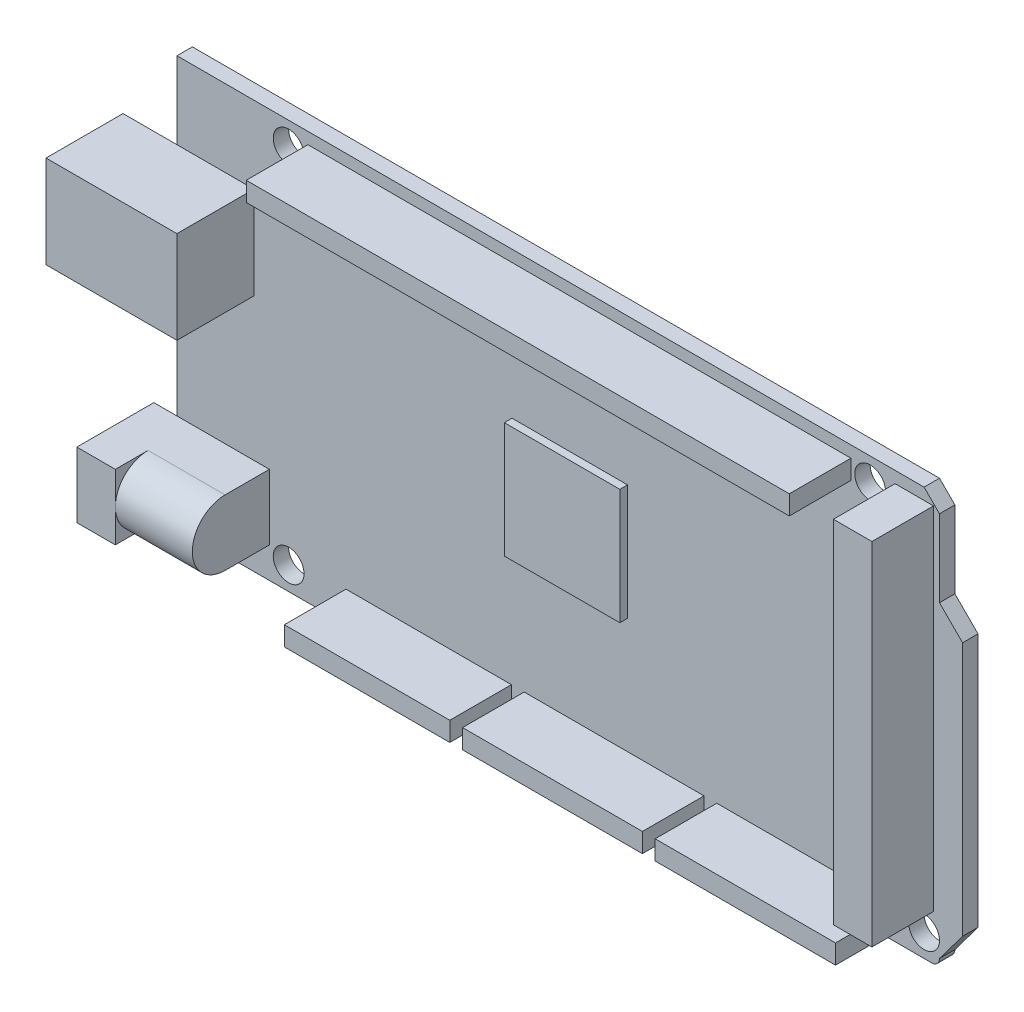
SolidWorks part; units mm, degrees
ref_plane "前视基准面" through (0, 0, 0) normal (0, 0, 1) x (1, 0, 0)
ref_plane "上视基准面" through (0, 0, 0) normal (0, 1, 0) x (1, 0, 0)
ref_plane "右视基准面" through (0, 0, 0) normal (1, 0, 0) x (0, 0, -1)
sketch "草图2" plane through (0, 0, 0) normal (0, 0, 1) x (1, 0, 0)
  line L1 (-51, 26.5) -> (51, 26.5)
  line L2 (-51, 26.5) -> (-51, -26.5)
  line L3 (-51, -26.5) -> (51, -26.5)
  line L4 (51, 26.5) -> (51, -26.5)
  line L5 (-51, 26.5) -> (51, -26.5) construction
  line L6 (-51, -26.5) -> (51, 26.5) construction
  point P0 (0, 0)
  dimension "D1" = 102
  dimension "D2" = 53
extrude "凸台-拉伸1" add sketch "草图2" along normal blind 2
sketch "草图3" plane through (0, 0, 2) normal (0, 0, 1) x (1, 0, 0)
  line L0 (51, 11.5) -> (48, 14.5)
  line L2 (48, 14.5) -> (48, 24.5)
  line L3 (51, -26.5) -> (51, 26.5) construction
  line L5 (51, -21.5) -> (48, -25.5)
  line L6 (48, -25.5) -> (48, -26.5)
  line L7 (-51, -26.5) -> (51, -26.5) construction
  line L8 (48, 24.5) -> (46, 26.5)
  line L9 (51, 26.5) -> (-51, 26.5) construction
  line L10 (48, -26.5) -> (51, -26.5)
  line L11 (51, -26.5) -> (51, -21.5)
  line L12 (46, 26.5) -> (51, 26.5)
  line L13 (51, 26.5) -> (51, 11.5)
  dimension "D1" = 15
  dimension "D2" = 3
  dimension "D3" = 135
  dimension "D4" = 2
  dimension "D5" = 3
  dimension "D6" = 3
  dimension "D7" = 5
  dimension "D8" = 1
extrude "切除-拉伸1" cut sketch "草图3" against normal blind 2
sketch "草图4" plane through (0, 0, 2) normal (0, 0, 1) x (1, 0, 0)
  line L0 (-51, -26.5) -> (48, -26.5) construction
  line L1 (51, -21.5) -> (51, 11.5) construction
  circle A0 centre (46, -23.5) radius 2
  dimension "D2" = 4
  dimension "D1" = 3
  dimension "D3" = 5
extrude "切除-拉伸2" cut sketch "草图4" against normal blind 2
fillet "圆角1" radius 1 1 edges at (48, -26.5, 1)
sketch "草图5" plane through (0, 0, 2) normal (0, 0, 1) x (1, 0, 0)
  line L0 (48, 24.5) -> (48, 14.5) construction
  line L1 (46, 26.5) -> (-51, 26.5) construction
  line L2 (-51, 26.5) -> (-51, -26.5) construction
  line L3 (-51, 0) -> (-23.0859, 0) construction
  circle A0 centre (39, 23.5) radius 2
  circle A1 centre (-36.5, 23.5) radius 2
  circle A2 centre (-36.5, -23.5) radius 2
  dimension "D1" = 4
  dimension "D6" = 4
  dimension "D2" = 9
  dimension "D3" = 3
  dimension "D4" = 3
  dimension "D5" = 14.5
extrude "切除-拉伸3" cut sketch "草图5" against normal blind 2
sketch "草图6" plane through (0, 0, 2) normal (0, 0, 1) x (1, 0, 0)
  line L0 (46, 26.5) -> (-51, 26.5) construction
  line L1 (-58, 16.5) -> (-41, 16.5)
  line L2 (-58, 16.5) -> (-58, 4.5)
  line L3 (-58, 4.5) -> (-41, 4.5)
  line L4 (-41, 16.5) -> (-41, 4.5)
  line L5 (-51, 26.5) -> (-51, -26.5) construction
  dimension "D1" = 12
  dimension "D2" = 10
  dimension "D3" = 10
  dimension "D4" = 17
extrude "凸台-拉伸2" add sketch "草图6" along normal blind 10
sketch "草图7" plane through (0, 0, 2) normal (0, 0, 1) x (1, 0, 0)
  line L0 (46, 26.5) -> (-51, 26.5) construction
  line L1 (-34, 25) -> (36.5, 25)
  line L2 (-34, 25) -> (-34, 22.5)
  line L3 (-34, 22.5) -> (36.5, 22.5)
  line L4 (36.5, 25) -> (36.5, 22.5)
  line L5 (-51, -26.5) -> (47, -26.5) construction
  line L6 (42.2266, 25) -> (47.2266, 25)
  line L7 (42.2266, 25) -> (42.2266, -20.5979)
  line L8 (42.2266, -20.5979) -> (47.2266, -20.5979)
  line L9 (47.2266, 25) -> (47.2266, -20.5979)
  line L10 (-29.0529, -22.5) -> (42.5, -22.5)
  line L11 (-29.0529, -22.5) -> (-29.0529, -25)
  line L12 (-29.0529, -25) -> (42.5, -25)
  line L13 (42.5, -22.5) -> (42.5, -25)
  circle A0 centre (39, 23.5) radius 2 construction
  circle A1 centre (-36.5, 23.5) radius 2 construction
  circle A2 centre (46, -23.5) radius 2 construction
  dimension "D8" = 3.5
  dimension "D1" = 2.5
  dimension "D2" = 1.5
  dimension "D3" = 2.5
  dimension "D4" = 2.5
  dimension "D5" = 5
  dimension "D6" = 2.5
  dimension "D7" = 1.5
extrude "凸台-拉伸3" add sketch "草图7" along normal blind 8
sketch "草图8" plane through (0, 0, 2) normal (0, 0, 1) x (1, 0, 0)
  line L1 (-7.5, 7.5) -> (7.5, 7.5)
  line L2 (-7.5, 7.5) -> (-7.5, -7.5)
  line L3 (-7.5, -7.5) -> (7.5, -7.5)
  line L4 (7.5, 7.5) -> (7.5, -7.5)
  line L5 (-7.5, 7.5) -> (7.5, -7.5) construction
  line L6 (-7.5, -7.5) -> (7.5, 7.5) construction
  point P0 (0, 0)
  dimension "D1" = 15
  dimension "D2" = 15
extrude "凸台-拉伸4" add sketch "草图8" along normal blind 1
sketch "草图9" plane through (0, 0, 10) normal (0, 0, 1) x (1, 0, 0)
  line L2 (-7.5741, -22.5) -> (-5.9194, -22.5)
  line L3 (-7.5741, -22.5) -> (-7.5741, -25)
  line L4 (-7.5741, -25) -> (-5.9194, -25)
  line L6 (42.5, -22.5) -> (-29.0529, -22.5) construction
  line L7 (17.431, -22.5) -> (19.0858, -22.5)
  line L8 (17.431, -22.5) -> (17.431, -25)
  line L9 (17.431, -25) -> (19.0858, -25)
  line L10 (19.0858, -22.5) -> (19.0858, -25)
  line L11 (-29.0529, -25) -> (42.5, -25) construction
  line L12 (-5.9194, -22.5) -> (-5.9194, -25)
extrude "切除-拉伸4" cut sketch "草图9" against normal blind 8
sketch "草图10" plane through (0, 0, 2) normal (0, 0, 1) x (1, 0, 0)
  line L0 (-51, -26.5) -> (47, -26.5) construction
  line L1 (-54, -14) -> (-39, -14)
  line L2 (-54, -14) -> (-54, -22.5)
  line L3 (-54, -22.5) -> (-39, -22.5)
  line L4 (-39, -14) -> (-39, -22.5)
  line L5 (-51, 4.5) -> (-51, -26.5) construction
  dimension "D1" = 4
  dimension "D2" = 12
  dimension "D3" = 8.5
  dimension "D4" = 3
extrude "凸台-拉伸5" add sketch "草图10" along normal blind 10
sketch "草图11" plane through (-39, 0, 0) normal (1, 0, 0) x (0, 0, -1)
  line L0 (-12, -22.5) -> (-12, -14) construction
  line L1 (-12, -14) -> (-7.75, -14)
  line L2 (-12, -18.25) -> (-12, -22.5)
  line L3 (-12, -22.5) -> (-7.75, -22.5)
  arc A0 (-7.75, -14) -> (-7.75, -22.5) centre (-7.75, -18.25) ccw
  line M2 (-2, -14) -> (-12, -14)
  line M3 (-12, -14) -> (-12, -22.5)
  line M4 (-12, -22.5) -> (-2, -22.5)
  dimension "D1" = 4.25
extrude "切除-拉伸5" cut sketch "草图11" against normal blind 10 contours A0 M3 M4 | A0 M2 M3 region at (-39, -21.5507, 11.0507) region at (-39, -14.9493, 11.0507)
sketch "草图12" plane through (-54, 0, 0) normal (-1, 0, 0) x (0, 0, 1)
  line L0 (12, -14) -> (12, -22.5) construction
  circle A0 centre (7.75, -18.25) radius 3
  circle A1 centre (7.75, -18.25) radius 0.5
  dimension "D2" = 6
  dimension "D3" = 1
  dimension "D1" = 4.25
extrude "切除-拉伸6" cut sketch "草图12" against normal blind 11
sketch "草图13" plane through (-58, 0, 0) normal (-1, 0, 0) x (0, 0, 1)
  line L0 (11, 13.5) -> (9, 15.5)
  line L1 (9, 5.5) -> (11, 7.5)
  line L3 (5.5, 12.5) -> (8.5, 12.5)
  line L4 (5.5, 12.5) -> (5.5, 8.5)
  line L5 (5.5, 8.5) -> (8.5, 8.5)
  line L6 (8.5, 12.5) -> (8.5, 8.5)
  line L8 (3, 15.5) -> (3, 5.5)
  line L9 (3, 5.5) -> (11, 5.5)
  line L10 (11, 5.5) -> (11, 15.5)
  line L11 (11, 15.5) -> (3, 15.5)
  line L12 (3, 15.5) -> (3, 5.5)
  line L13 (3, 5.5) -> (9, 5.5)
  line L14 (11, 7.5) -> (11, 13.5)
  line L15 (9, 15.5) -> (3, 15.5)
  dimension "D2" = 3
  dimension "D3" = 3
  dimension "D4" = 2.5
  dimension "D5" = 2.5
  dimension "D1" = 1
extrude "切除-拉伸7" cut sketch "草图13" against normal blind 11
